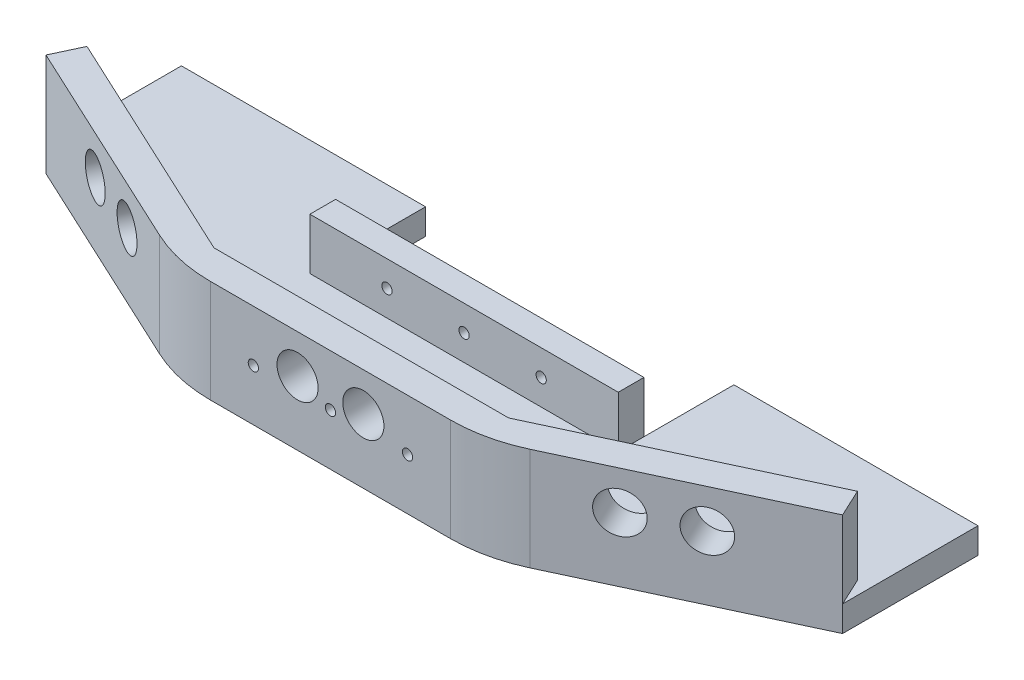
SolidWorks part; units mm, degrees
ref_plane "前视基准面" through (0, 0, 0) normal (0, 0, 1) x (1, 0, 0)
ref_plane "上视基准面" through (0, 0, 0) normal (0, 1, 0) x (1, 0, 0)
ref_plane "右视基准面" through (0, 0, 0) normal (1, 0, 0) x (0, 0, -1)
sketch "Sketch1" plane through (0, 0, 0) normal (0, 1, 0) x (1, 0, 0)
  line L0 (-60, 0) -> (60, 0)
  line L1 (60, 0) -> (155, 44.2992)
  line L2 (0, 0) -> (0, 297.9747) construction
  line L3 (-60, 0) -> (-155, 44.2992)
  point P4 (0, 0)
  dimension "D1" = 120
  dimension "D2" = 155
  dimension "D3" = 95
extrude "Extrude-Thin1" add sketch "Sketch1" along normal blind 30 thin thin type one direction wall 12
sketch "Sketch2" plane through (10.7164, 0, 22.9813) normal (0.4226, 0, 0.9063) x (0.9063, 0, -0.4226)
  line L0 (106.7889, 30) -> (106.7889, 0) construction
  line L1 (159.1994, 30) -> (54.3785, 30) construction
  line L2 (159.1994, 0) -> (54.3785, 0) construction
  line L3 (93.9889, 15) -> (119.5889, 15) construction
  circle A0 centre (93.9889, 15) radius 8
  circle A1 centre (119.5889, 15) radius 8
  point P9 (106.7889, 15)
  dimension "D2" = 16
  dimension "D3" = 16
  dimension "D1" = 25.6
extrude "Cut-Extrude1" cut sketch "Sketch2" against normal through all
mirror "Mirror1" about plane through (0, 0, 0) normal (1, 0, 0) of "Cut-Extrude1"
sketch "Sketch3" plane through (0, 0, 0) normal (0, 0, 1) x (1, 0, 0)
  line L0 (0, 0) -> (0, 30) construction
  line L1 (60, 30) -> (-60, 30) construction
  line L2 (-12.8, 15) -> (12.8, 15) construction
  circle A0 centre (12.8, 15) radius 8
  circle A1 centre (-12.8, 15) radius 8
  point P8 (0, 15)
  dimension "D2" = 16
  dimension "D1" = 25.6
extrude "Cut-Extrude2" cut sketch "Sketch3" against normal through all
sketch "Sketch4" plane through (0, 30, 0) normal (0, 1, 0) x (1, 0, 0)
  line L0 (0, 0) -> (0, -1000) construction
  line L1 (0, 0) -> (-267.9492, -1000) construction
  line L2 (0, 0) -> (267.9492, -1000) construction
  line L3 (60.3367, -1000) -> (-60.3367, -1000)
  line L4 (-60, 0) -> (-60, -1000) construction
  line L5 (60, 0) -> (60, -1000) construction
  line L6 (107.5, 22.1496) -> (530.1183, -884.1582) construction
  line L7 (155, 44.2992) -> (60, 0) construction
  line L8 (287.2731, -997.3987) -> (772.9634, -770.9176)
  point P8 (0, -1000)
  point P9 (0, 0)
  point P12 (0, 0)
  point P22 (530.1183, -884.1582)
  point P23 (0, 0)
  dimension "D1" = 15
  dimension "D2" = 15
  dimension "D3" = 1000
  dimension "D4" = 535.9
  dimension "D5" = 1000
sketch "Sketch5" plane through (0, 0, 0) normal (0, -1, 0) x (1, 0, 0)
  line L0 (0, 0) -> (0, -53.5875) construction
  line L1 (0, 0) -> (0, 1000) construction
  line L2 (149.9286, -55.1749) -> (-149.9286, -55.1749)
  line L3 (-60, -52) -> (60, -52)
  line L4 (-60, -52) -> (-60, -55.1749)
  line L5 (-60, -55.1749) -> (60, -55.1749)
  line L6 (60, -52) -> (60, -55.1749)
  line L7 (-60, -52) -> (60, -55.1749) construction
  line L8 (-60, -55.1749) -> (60, -52) construction
  line L9 (60, -52) -> (66.8086, -55.1749)
  line L10 (149.9286, -55.1749) -> (57.3397, -12) construction
  line L11 (57.3397, -12) -> (-57.3397, -12) construction
  line L12 (-60, -52) -> (-66.8086, -55.1749)
  line M8 (-149.9286, -55.1749) -> (-57.3397, -12)
  line M9 (-57.3397, -12) -> (57.3397, -12)
  line M10 (57.3397, -12) -> (149.9286, -55.1749)
  line M11 (149.9286, -55.1749) -> (155, -44.2992)
  line M12 (155, -44.2992) -> (60, 0)
  line M13 (60, 0) -> (-60, 0)
  line M14 (-60, 0) -> (-155, -44.2992)
  line M15 (-155, -44.2992) -> (-149.9286, -55.1749)
  dimension "D1" = 120
  dimension "D2" = 40
extrude "Boss-Extrude1" add sketch "Sketch5" along normal blind 10 contours L12 L3 L9 L2 M10 M9 M8 | M15 M8 M9 M10 M11 M12 M13 M14 region at (0, 0, -36.0098) region at (104.9648, 0, -30.7338)
sketch "Sketch7" plane through (0, 0, -52) normal (0, 0, -1) x (-1, 0, 0)
  line L0 (60, -10) -> (60, 0) construction
  line L1 (-60, -10) -> (60, -10)
  line L2 (-60, -10) -> (-60, 20)
  line L3 (-60, 20) -> (60, 20)
  line L4 (60, -10) -> (60, 20)
  line L5 (-57.3397, 0) -> (57.3397, 0) construction
  dimension "D1" = 20
extrude "Boss-Extrude2" add sketch "Sketch7" along normal blind 10
sketch "Sketch8" plane through (0, 0, -62) normal (0, 0, -1) x (-1, 0, 0)
  line L0 (-60, 10) -> (60, 10) construction
  line L1 (-60, 20) -> (-60, -10) construction
  line L2 (60, -10) -> (60, 20) construction
  line L3 (60, 20) -> (-60, 20) construction
  line L4 (0, 10) -> (0, 0) construction
  circle A0 centre (0, 10) radius 2
  circle A1 centre (-30, 10) radius 2
  circle A2 centre (30, 10) radius 2
  dimension "D2" = 4
  dimension "D3" = 4
  dimension "D4" = 30
  dimension "D1" = 10
extrude "Cut-Extrude3" cut sketch "Sketch8" against normal through all
sketch "Sketch9" plane through (0, 0, 0) normal (0, 1, 0) x (1, 0, 0)
  line L0 (-60, 62) -> (-60, 97) construction
  line L1 (60, 62) -> (60, 97) construction
  line L2 (60, 97) -> (-60, 97) construction
  line L3 (0, 0) -> (0, 97) construction
  line L4 (60, 97) -> (155, 97)
  line L5 (60, 97) -> (60, 44.2992)
  line L6 (60, 44.2992) -> (155, 44.2992)
  line L7 (155, 97) -> (155, 44.2992)
  point P17 (155, 44.2992)
  dimension "D1" = 35
fillet "Fillet1" radius 60 2 edges at (-60, 10, 0) (60, 10, 0)
extrude "Boss-Extrude3" add sketch "Sketch9" against normal blind 10
mirror "Mirror2" about plane through (0, 0, 0) normal (1, 0, 0) of "Boss-Extrude3"
sketch "Sketch10" plane through (5.645, 0, 12.1056) normal (-0.4226, 0, -0.9063) x (-0.9063, 0, 0.4226)
  line L0 (-106.7889, 30) -> (-106.7889, 0) construction
  line L1 (161.1611, 30) -> (-374.7389, 30) construction
  line L2 (-95.3724, 0) -> (-181.4717, 0) construction
  line L3 (-159.1994, 0) -> (-57.0388, 0) construction
  line L4 (-112.2889, 21.3) -> (-101.2889, 21.3)
  line L5 (-112.2889, 21.3) -> (-112.2889, 25.3)
  line L6 (-112.2889, 25.3) -> (-101.2889, 25.3)
  line L7 (-101.2889, 21.3) -> (-101.2889, 25.3)
  line L8 (-112.2889, 21.3) -> (-101.2889, 25.3) construction
  line L9 (-112.2889, 25.3) -> (-101.2889, 21.3) construction
  line L10 (-112.2889, 4.7) -> (-101.2889, 4.7)
  line L11 (-112.2889, 4.7) -> (-112.2889, 9.7)
  line L12 (-112.2889, 9.7) -> (-101.2889, 9.7)
  line L13 (-101.2889, 4.7) -> (-101.2889, 9.7)
  line L14 (-112.2889, 4.7) -> (-101.2889, 9.7) construction
  line L15 (-112.2889, 9.7) -> (-101.2889, 4.7) construction
  point P6 (-106.7889, 23.3)
  point P11 (-106.7889, 7.2)
  dimension "D1" = 11
  dimension "D2" = 4
  dimension "D3" = 4.7
  dimension "D4" = 5
  dimension "D5" = 11
  dimension "D6" = 4.7
extrude "Cut-Extrude4" cut sketch "Sketch10" against normal blind 4.5
mirror "Mirror3" about plane through (0, 0, 0) normal (1, 0, 0) of "Cut-Extrude4"
sketch "Sketch13" plane through (0, 0, -12) normal (0, 0, -1) x (-1, 0, 0)
  line L0 (0, 0) -> (0, 30) construction
  line L1 (-60.3367, 30) -> (60.3367, 30) construction
  line L3 (-5.5, 4.7) -> (5.5, 4.7)
  line L4 (-5.5, 4.7) -> (-5.5, 9.7)
  line L5 (-5.5, 9.7) -> (5.5, 9.7)
  line L6 (5.5, 4.7) -> (5.5, 9.7)
  line L7 (-5.5, 4.7) -> (5.5, 9.7) construction
  line L8 (-5.5, 9.7) -> (5.5, 4.7) construction
  line L9 (-5.5, 25.3) -> (5.5, 25.3)
  line L10 (-5.5, 25.3) -> (-5.5, 21.3)
  line L11 (-5.5, 21.3) -> (5.5, 21.3)
  line L12 (5.5, 25.3) -> (5.5, 21.3)
  line L13 (-5.5, 25.3) -> (5.5, 21.3) construction
  line L14 (-5.5, 21.3) -> (5.5, 25.3) construction
  line L15 (-149.9286, 0) -> (-57.3397, 0) construction
  point P5 (0, 7.2)
  point P10 (0, 23.3)
  dimension "D1" = 4.7
  dimension "D2" = 4.7
  dimension "D3" = 5
  dimension "D4" = 11
  dimension "D5" = 11
  dimension "D6" = 4
extrude "Cut-Extrude5" cut sketch "Sketch13" against normal blind 4
